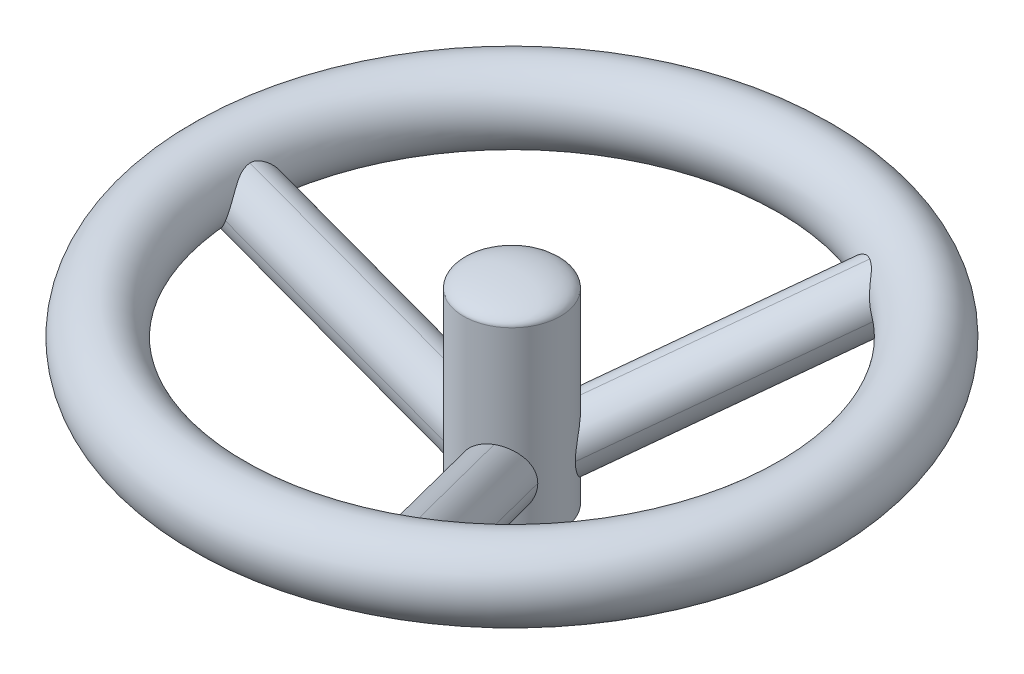
SolidWorks part; units mm, degrees
ref_plane "Front Plane" through (0, 0, 0) normal (0, 0, 1) x (1, 0, 0)
ref_plane "Top Plane" through (0, 0, 0) normal (0, 1, 0) x (1, 0, 0)
ref_plane "Right Plane" through (0, 0, 0) normal (1, 0, 0) x (0, 0, -1)
sketch "Sketch1" plane through (0, 0, 0) normal (0, 0, 1) x (1, 0, 0)
  line L2 (0, -98.1318) -> (33.1271, -98.1318)
  line L3 (0, -98.1318) -> (0, 28.8435)
  line L4 (0, 28.8435) -> (33.1271, 28.8435)
  line L5 (33.1271, -98.1318) -> (33.1271, 28.8435)
  circle A0 centre (200, 0) radius 25
  dimension "D2" = 50
revolve "Revolve1" add sketch "Sketch1" angle 360 about L3
dome "Dome1" faces to dome 1 distance 10 reverse direction no elliptical dome yes face at (0, 28.8435, -33.1271) parameters "D1"=10
sketch "Sketch2" plane through (0, 0, 0) normal (0, 0, 1) x (1, 0, 0)
  line L1 (-206.9928, -18.7377) -> (-32.6276, -83.8096)
  line L2 (-193.0072, 18.7377) -> (-18.642, -46.3343)
  line L3 (-193.0072, 18.7377) -> (-206.9928, -18.7377)
  line L4 (-18.642, -46.3343) -> (-5.4065, -51.2737)
  line L5 (-5.4065, -51.2737) -> (-19.392, -88.749)
  line L6 (-19.392, -88.749) -> (-32.6276, -83.8096)
extrude "Boss-Extrude1" add sketch "Sketch2" along normal blind 20 and the other way blind 20 separate body
fillet "Fillet1" radius 20 3 edges at (-113.1924, -53.7434, -20) (-99.2068, -16.268, 20) (-113.1924, -53.7434, 20)
fillet "Fillet2" radius 20 1 edges at (-99.2068, -16.268, -20)
pattern_circular "CirPattern2" count 3 over 360 about axis through (0, -98.1318, 0) along (0, -1, 0) of bodies 103
